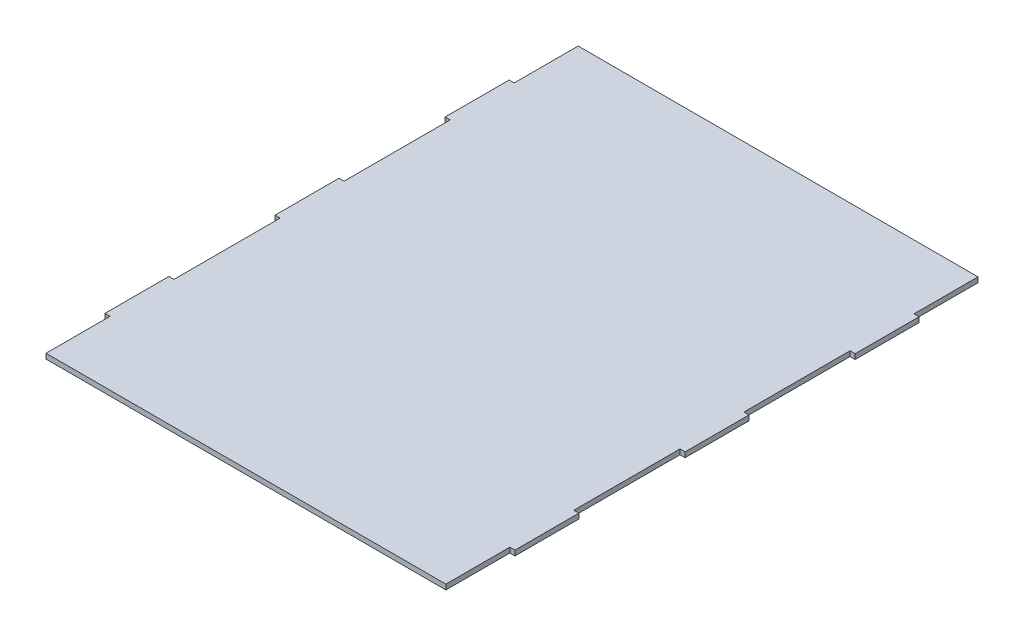
SolidWorks part; units mm, degrees
ref_plane "前视" through (0, 0, 0) normal (0, 0, 1) x (1, 0, 0)
ref_plane "上视" through (0, 0, 0) normal (0, 1, 0) x (1, 0, 0)
ref_plane "右视" through (0, 0, 0) normal (1, 0, 0) x (0, 0, -1)
sketch "Sketch1" plane through (0, 0, 0) normal (0, 1, 0) x (1, 0, 0)
  line L1 (0, 0) -> (250, 0)
  line L2 (0, 0) -> (0, -332.7)
  line L3 (0, -332.7) -> (250, -332.7)
  line L4 (250, 0) -> (250, -332.7)
  dimension "D1" = 332.7
  dimension "D2" = 250
extrude "Boss-Extrude1" add sketch "Sketch1" along normal blind 3.175
sketch "Sketch2" plane through (0, 3.175, 0) normal (0, 1, 0) x (1, 0, 0)
  line L0 (0, 0) -> (0, -332.7) construction
  line L1 (0, -40) -> (-3.175, -40)
  line L2 (0, -40) -> (0, -80)
  line L3 (0, -80) -> (-3.175, -80)
  line L4 (-3.175, -40) -> (-3.175, -80)
  line L5 (250, 0) -> (0, 0) construction
  line L6 (250, -332.7) -> (250, 0) construction
  line L7 (250, -40) -> (253.175, -40)
  line L8 (250, -40) -> (250, -80)
  line L9 (250, -80) -> (253.175, -80)
  line L10 (253.175, -40) -> (253.175, -80)
  dimension "D1" = 40
  dimension "D2" = 40
  dimension "D3" = 3.175
  dimension "D4" = 3.175
extrude "Boss-Extrude2" add sketch "Sketch2" against normal up to surface (3.175 mm away) up to face at (125, 0, 166.35)
pattern_linear "LPattern1" count 3 spacing 106.35 along (0, 0, 1) of "Boss-Extrude2"
